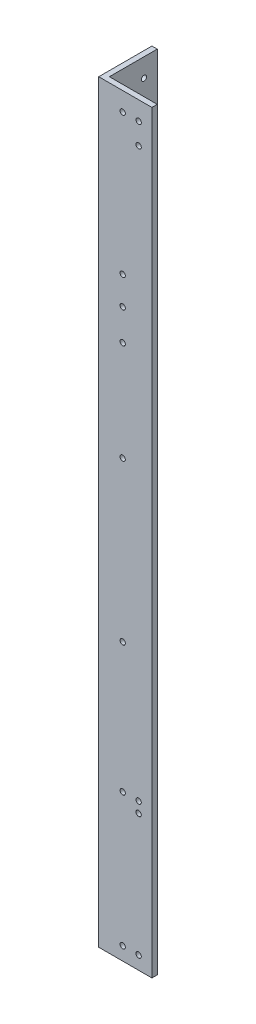
SolidWorks part; units mm, degrees
ref_plane "Front Plane" through (0, 0, 0) normal (0, 0, 1) x (1, 0, 0)
ref_plane "Top Plane" through (0, 0, 0) normal (0, 1, 0) x (1, 0, 0)
ref_plane "Right Plane" through (0, 0, 0) normal (1, 0, 0) x (0, 0, -1)
sketch "Sketch2" plane through (0, 0, 0) normal (0, 1, 0) x (1, 0, 0)
  line L0 (0, 31.75) -> (3.175, 31.75)
  line L1 (3.175, 31.75) -> (3.175, 3.175)
  line L2 (3.175, 3.175) -> (31.75, 3.175)
  line L3 (31.75, 3.175) -> (31.75, 0)
  line L4 (31.75, 0) -> (0, 0)
  line L5 (0, 0) -> (0, 31.75)
  point P9 (1.5875, 31.75)
  point P10 (31.75, 1.5875)
  dimension "D4" = 3.175
  dimension "D1" = 31.75
  dimension "D2" = 31.75
  dimension "D3" = 3.175
extrude "Boss-Extrude1" add sketch "Sketch2" along normal blind 450
sketch "FrontSideHoles-Sketch3" plane through (0, 0, 0) normal (0, 0, 1) x (1, 0, 0)
  line L0 (0, 0) -> (31.75, 0) construction
  line L1 (0, 450) -> (0, 0) construction
  circle A1 centre (23.8125, 81.1125) radius 1.5875
  circle A2 centre (14.2875, 87.4625) radius 1.5875
  circle A3 centre (23.8125, 87.4625) radius 1.5875
  circle A4 centre (14.2875, 438.8875) radius 1.5875
  circle A6 centre (23.8125, 438.8875) radius 1.5875
  circle A7 centre (23.8125, 426.1875) radius 1.5875
  circle A8 centre (14.2875, 338.1776) radius 1.5875
  circle A9 centre (14.2875, 319.6526) radius 1.5875
  circle A10 centre (14.2875, 260) radius 1.5875
  circle A11 centre (14.2875, 165) radius 1.5875
  circle A12 centre (14.2875, 355) radius 1.5875
  circle A13 centre (14.2875, 7.9375) radius 1.5875
  circle A14 centre (23.8125, 7.9375) radius 1.5875
  dimension "D4" = 3.175
  dimension "D8" = 11.1125
  dimension "D11" = 18.525
  dimension "D9" = 319.6526
  dimension "D6" = 165
  dimension "D10" = 95
  dimension "D13" = 95
  dimension "D12" = 7.9375
  dimension "D3" = 9.525
  dimension "D2" = 14.2875
  dimension "D5" = 6.35
  dimension "D14" = 81.1125
  dimension "D7" = 12.7
sketch "LeftSideHoles-Sketch4" plane through (0, 0, 0) normal (-1, 0, 0) x (0, 0, 1)
  line L0 (-31.75, 450) -> (0, 450) construction
  line L1 (0, 450) -> (0, 0) construction
  line L3 (-31.75, 0) -> (0, 0) construction
  circle A0 centre (-23.8125, 81.1125) radius 1.5875
  circle A1 centre (-14.2875, 81.1125) radius 1.5875
  circle A2 centre (-23.8125, 87.4625) radius 1.5875
  circle A4 centre (-23.8125, 438.8875) radius 1.5875
  circle A6 centre (-23.8125, 426.1875) radius 1.5875
  circle A7 centre (-14.2875, 426.1875) radius 1.5875
  circle A8 centre (-23.8125, 332.6026) radius 1.5875
  circle A9 centre (-14.2875, 332.6026) radius 1.5875
  circle A10 centre (-23.8125, 319.9026) radius 1.5875
  circle A11 centre (-14.2875, 319.9026) radius 1.5875
  circle A12 centre (-23.8125, 7.9375) radius 1.5875
  circle A13 centre (-14.2875, 7.9375) radius 1.5875
  circle A14 centre (-14.2875, 165) radius 1.5875
  circle A15 centre (-14.2875, 260) radius 1.5875
  circle A16 centre (-14.2875, 355) radius 1.5875
  dimension "D4" = 3.175
  dimension "D13" = 95
  dimension "D2" = 14.2875
  dimension "D5" = 6.35
  dimension "D7" = 12.7
  dimension "D3" = 81.1125
  dimension "D6" = 11.1125
  dimension "D10" = 7.9375
  dimension "D9" = 12.7
  dimension "D11" = 9.525
  dimension "D8" = 332.6026
  dimension "D12" = 165
  dimension "D14" = 95
extrude "FrontSideHoles-Cut-Extrude1" cut sketch "FrontSideHoles-Sketch3" against normal blind 3.175
extrude "LeftSideHoles-Cut-Extrude2" cut sketch "LeftSideHoles-Sketch4" against normal blind 3.175
equation "\"RailThickness\"= .125in'Spec"
equation "\"VSWidth\"= 1.25in'Spec"
equation "\"VSHeight\"= 1.25in'Spec"
equation "\"VSLength\"= 450mm"
equation "\"HoleOffsetFromEdge\"= \"RailThickness\" * 2.5"
equation "\"HoleOffsetFromSide\"= \"RailThickness\" * 3.5"
equation "\"LegHeight\"= 70mm'Space needed for PSU/Stepper/Electronics"
equation "\"VSBottomSideRailHoleY1FromBottomOfLowerRail\"= \"V1 BottomOfLowerRail\" + \"HoleOffsetFromSide\"'Equals 70.1125"
equation "\"VSSideRailHoleX1FromSide\"= \"HoleOffsetFromSide\" + \"RailThickness\""
equation "\"FasteningHoleDiameter\"= .125in"
equation "\"VSBottomSideRailHoleY2FromY1\"= \"LowerRailHeight\" - \"HoleOffsetFromSide\" - \"HoleOffsetFromEdge\"'Equals 6.35"
equation "\"VSTopSideRailHoleY1FromEdge\"= \"HoleOffsetFromEdge\" + \"RailThickness\""
equation "\"D4@FrontSideHoles-Sketch3\" = \"FasteningHoleDiameter\""
equation "\"D1@Boss-Extrude1\"=\"VSLength\""
equation "\"D4@LeftSideHoles-Sketch4\" = \"FasteningHoleDiameter\""
equation "\"D3@LeftSideHoles-Sketch4\"= \"VSBottomSideRailHoleY1FromBottomOfLowerRail\""
equation "\"D8@FrontSideHoles-Sketch3\" = \"VSTopSideRailHoleY1FromEdge\""
equation "\"D6@LeftSideHoles-Sketch4\" = \"VSTopSideRailHoleY1FromEdge\""
equation "\"VSMidSideRailHoleY1FromV8TopOfMidSideRail\"= \"V8 ToTopOfMidSideRail\" - \"HoleOffsetFromEdge\"'Equals 308.2875"
equation "\"LowerRailHeight\"= 1.00in"
equation "\"D1@Sketch2\"=\"VSHeight\""
equation "\"D2@Sketch2\"=\"VSWidth\""
equation "\"TopRailHeight\"= 1.25in"
equation "\"MidSideRailHeight\"= 1.25in"
equation "\"D10@LeftSideHoles-Sketch4\"=\"HoleOffsetFromEdge\""
equation "\"VSMidSideRailHoleY2FromY1\"= \"MidSideRailHeight\" - \"HoleOffsetFromSide\" - \"HoleOffsetFromEdge\"'Equals 12.7"
equation "\"D9@LeftSideHoles-Sketch4\"=\"VSMidSideRailHoleY2FromY1\""
equation "\"VSSideRailHoleX2FromX1\"= \"VSWidth\" - \"VSSideRailHoleX1FromSide\" - \"HoleOffsetFromEdge\""
equation "\"D11@LeftSideHoles-Sketch4\"=\"VSSideRailHoleX2FromX1\""
equation "\"VSTopSideRailHoleY2FromY1\"= \"TopRailHeight\" - \"VSTopSideRailHoleY1FromEdge\" - \"HoleOffsetFromEdge\"'Equals 12.7"
equation "\"D7@LeftSideHoles-Sketch4\"=\"VSTopSideRailHoleY2FromY1\""
equation "\"BeltTensionerInnerHeight\"= \"20TGT2PulleyWidth\" * 2 + \"1mmSpacer\" * 3"
equation "\"20TGT2PulleyWidth\"= 8.7mm'The STL of the Pulley in the diagram is a bit larger"
equation "\"1mmSpacer\"= 1mm"
equation "\"BeltTensionerHeight\"= \"BeltTensionerInnerHeight\" + \"BeltTensionerUpperLowerWallThickness\" * 2"
equation "\"BeltTensionerUpperLowerWallThickness\"= 7mm"
equation "\"D11@FrontSideHoles-Sketch3\"=\"VSBeltTensionerHoleY2FromY1\""
equation "\"VSBeltTensionerHoleY1FromBottom\"= \"V9 FromBottomGantryPulleyToBottomOfBeltTensioner\" + \"HoleOffsetFromEdge\""
equation "\"VSBeltTensionerHoleY2FromY1\"= \"BeltTensionerHeight\" - \"HoleOffsetFromEdge\" * 2"
equation "\"V1 BottomOfLowerRail\"= \"LegHeight\""
equation "\"StepperShaftLength\"= 24mm'Pulley will be attached to the end"
equation "\"ZAxisLeadScrewLength\"= 200mm"
equation "\"LM8UUHeight\"= 24mm'Spec"
equation "\"V2 ToBedAtTopOfZAxis\"= \"V1 BottomOfLowerRail\" + \"StepperShaftLength\" + \"ZAxisLeadScrewLength\" - \"LM8UUHeight\" / 2"
equation "\"HotEndToTopOfXAxisGB\"= 63.315144mm'Measured from the100.Should be 63.315144"
equation "\"TopOfGBToBottomOfLinearRail\"= \"LinearGBWidth\" / 2 + \"LinearRailWidth\" / 2"
equation "\"LinearGBWidth\"= 27mm'Spec"
equation "\"V5 ToBottomOfXAxisLinearRail\"= \"V4 ToTopOfBuildPlate/HotEndTip\" + \"HotEndToTopOfXAxisGB\" - \"TopOfGBToBottomOfLinearRail\""
equation "\"LinearRailWidth\"= 12mm'Spec"
equation "\"V6 ToBottomOfGantryPulley\"= \"V5 ToBottomOfXAxisLinearRail\" - \"DistanceFromGABTopToLowerPulley\""
equation "\"GABUpperHeight\"= 6mm"
equation "\"GABMidWallHeight\"= 28mm'Must equal 28 or changes alignment"
equation "\"GABMidShortRiserHeight\"= \"GABMidWallHeight\" / 2 - \"20TGT2PulleyWidth\"'Equals 5.3"
equation "\"GABRiserBossOffset\"= 0.8mm'Aligns Pulleys"
equation "\"DistanceFromGABTopToLowerPulley\"= \"GABUpperHeight\" + \"GABMidWallHeight\" - \"GABMidShortRiserHeight\" + \"GABRiserBossOffset\" / 2"
equation "\"V7 ToTopOfMidBackRail\"= \"V6 ToBottomOfGantryPulley\" + \"StepperShaftLength\""
equation "\"D8@LeftSideHoles-Sketch4\"= \"VSMidSideRailHoleY1FromV8TopOfMidSideRail\""
equation "\"BedToBuildPlateStandoffLength\"= 15mm"
equation "\"BuildPlateHeight\"= 8mm'Spec"
equation "\"V4 ToTopOfBuildPlate/HotEndTip\"= \"V2 ToBedAtTopOfZAxis\" + \"BedToBuildPlateStandoffLength\" + \"BuildPlateHeight\""
equation "\"D9@FrontSideHoles-Sketch3\"=\"VSBeltTensionerHoleY1FromBottom\""
equation "\"V8 ToTopOfMidSideRail\"= \"V7 ToTopOfMidBackRail\" - \"RailThickness\""
equation "\"V9 FromBottomGantryPulleyToBottomOfBeltTensioner\"= \"V6 ToBottomOfGantryPulley\" - \"BeltTensionerUpperLowerWallThickness\" - \"1mmSpacer\""
equation "\"BeltTensionerMountingHoleOffsetFromEdge\"= \"HoleOffsetFromEdge\""
equation "\"VSBeltTensionerXMountingHoleOffsetFromSide\"= \"BeltTensionerMountingHoleOffsetFromEdge\" + \"RailThickness\" * 2"
equation "\"VSEnclosureOffsets\"= ( \"VSLength\" - \"LegHeight\" ) / 4"
equation "\"D6@FrontSideHoles-Sketch3\"=\"LegHeight\" + \"VSEnclosureOffsets\""
equation "\"D10@FrontSideHoles-Sketch3\"=\"VSEnclosureOffsets\""
equation "\"D13@FrontSideHoles-Sketch3\"=\"VSEnclosureOffsets\""
equation "\"D12@FrontSideHoles-Sketch3\"=\"HoleOffsetFromEdge\""
equation "\"D13@LeftSideHoles-Sketch4\"=\"VSEnclosureOffsets\""
equation "\"D14@LeftSideHoles-Sketch4\"=\"VSEnclosureOffsets\""
equation "\"D12@LeftSideHoles-Sketch4\"=\"LegHeight\" + \"VSEnclosureOffsets\""
equation "\"D3@FrontSideHoles-Sketch3\"=\"VSSideRailHoleX2FromX1\""
equation "\"D2@FrontSideHoles-Sketch3\"=\"VSSideRailHoleX1FromSide\""
equation "\"D5@FrontSideHoles-Sketch3\"=\"VSBottomSideRailHoleY2FromY1\""
equation "\"D14@FrontSideHoles-Sketch3\"=\"VSBottomSideRailHoleY1FromBottomOfLowerRail\""
equation "\"D7@FrontSideHoles-Sketch3\"=\"VSTopSideRailHoleY2FromY1\""
equation "\"D5@LeftSideHoles-Sketch4\"=\"VSBottomSideRailHoleY2FromY1\""
